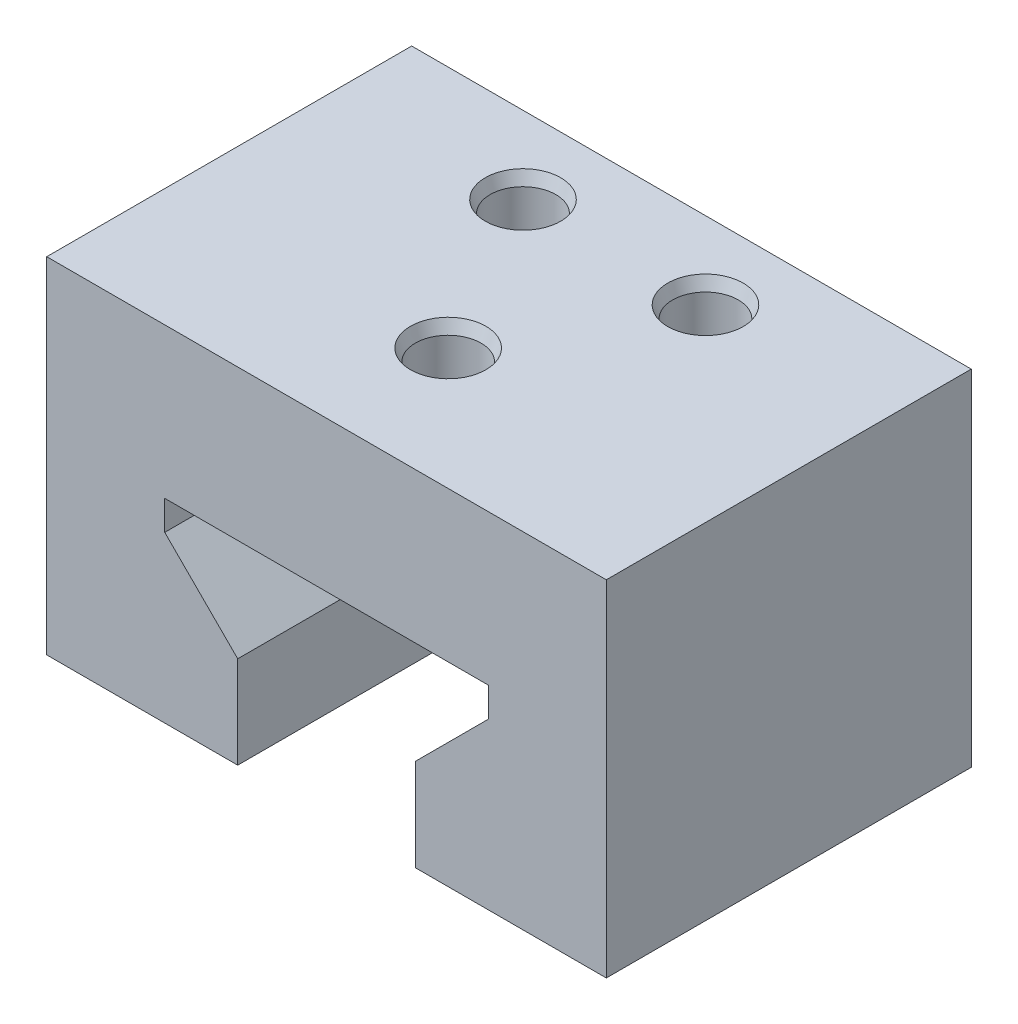
SolidWorks part; units mm, degrees
ref_plane "Front Plane" through (0, 0, 0) normal (0, 0, 1) x (1, 0, 0)
ref_plane "Top Plane" through (0, 0, 0) normal (0, 1, 0) x (1, 0, 0)
ref_plane "Right Plane" through (0, 0, 0) normal (1, 0, 0) x (0, 0, -1)
sketch "Sketch1" plane through (0, 0, 0) normal (0, 0, 1) x (1, 0, 0)
  line L0 (-7, 0) -> (7, 0) construction
  line L1 (-7, 0) -> (-7, 8) construction
  line L2 (-7, 8) -> (-13, 14) construction
  line L3 (-13, 14) -> (-13, 16) construction
  line L4 (13, 14) -> (7, 8) construction
  line L5 (7, 8) -> (7, 0) construction
  line L6 (-7.3, 0.3) -> (-7.3, 7.8757)
  line L10 (7.3, 7.8757) -> (7.3, 0.3)
  line L11 (7.3, 0.3) -> (23, 0.3)
  line L12 (23, 0.3) -> (23, 28.65)
  line L13 (23, 28.65) -> (-23, 28.65)
  line L14 (-23, 28.65) -> (-23, 0.3)
  line L15 (-23, 0.3) -> (-7.3, 0.3)
  line L16 (-13, 16) -> (13, 16) construction
  line L17 (13, 16) -> (13, 14) construction
  line L18 (-7.3, 7.8757) -> (-13.3, 13.8757)
  line L19 (-13.3, 13.8757) -> (-13.3, 16.3)
  line L20 (-13.3, 16.3) -> (13.3, 16.3)
  line L21 (13.3, 16.3) -> (13.3, 13.8757)
  line L22 (13.3, 13.8757) -> (7.3, 7.8757)
  point P4 (0, 0)
  point P22 (0, 16.3)
  point P23 (-13.3, 12.3586)
  point P24 (0, 0)
  point P25 (-13.3, 14)
  point P26 (-13.3, 12.4542)
  dimension "D1" = 14
  dimension "D2" = 8
  dimension "D3" = 26
  dimension "D4" = 0.3
  dimension "D5" = 0.3
  dimension "D6" = 0.3
  dimension "D7" = 0.3
  dimension "D8" = 2
  dimension "D9" = 0.3
  dimension "D10" = 0.3
  dimension "D11" = 46
  dimension "D12" = 6
  dimension "D13" = 0.3
  dimension "D14" = 0.3
  dimension "D15" = 12.35
extrude "Boss-Extrude1" add sketch "Sketch1" along normal blind 30
sketch "Sketch4" plane through (0, 28.65, 0) normal (0, 1, 0) x (1, 0, 0)
  line L0 (-7.5, -6.35) -> (7.5, -6.35) construction
  line L2 (-23, -30) -> (-23, 0) construction
  line L3 (0, -6.35) -> (0, -20) construction
  line L5 (23, -30) -> (-23, -30) construction
  point P0 (-7.5, -6.35)
  point P2 (7.5, -6.35)
  point P4 (0, -20)
  point P11 (0, -6.35)
  point P15 (-23, -15)
  dimension "D1" = 10
  dimension "D2" = 15
  dimension "D3" = 8.65
hole_wizard "Hole1" positions "Sketch4" profile "Sketch3" legacy end condition up to next
sketch "Sketch3" plane through (-7.5, 28.65, 6.35) normal (1, 0, 0) x (0, 0, 1)
  line L0 (0, 0) -> (0, 12.35)
  line L1 (0, 12.35) -> (2.7, 12.35)
  line L2 (2.7, 12.35) -> (2.7, 1)
  line L3 (2.7, 1) -> (3.1, 1)
  line L4 (3.1, 1) -> (3.1, 0)
  line L5 (3.1, 0) -> (0, 0)
  line L6 (0, 110) -> (0, -10) construction
  dimension "Diameter" = 5.4
  dimension "Depth" = 12.35
  dimension "C-Bore Diameter" = 6.2
  dimension "C-Bore Depth" = 1
chamfer "Chamfer1" distance 1 distance2 0.4 3 edges at (0, 27.65, 23.1) (7.5, 27.65, 9.45) (-7.5, 27.65, 9.45) first distance on face at (0, 27.65, 23.1) first distance on face at (7.5, 27.65, 9.45) first distance on face at (-7.5, 27.65, 9.45)
